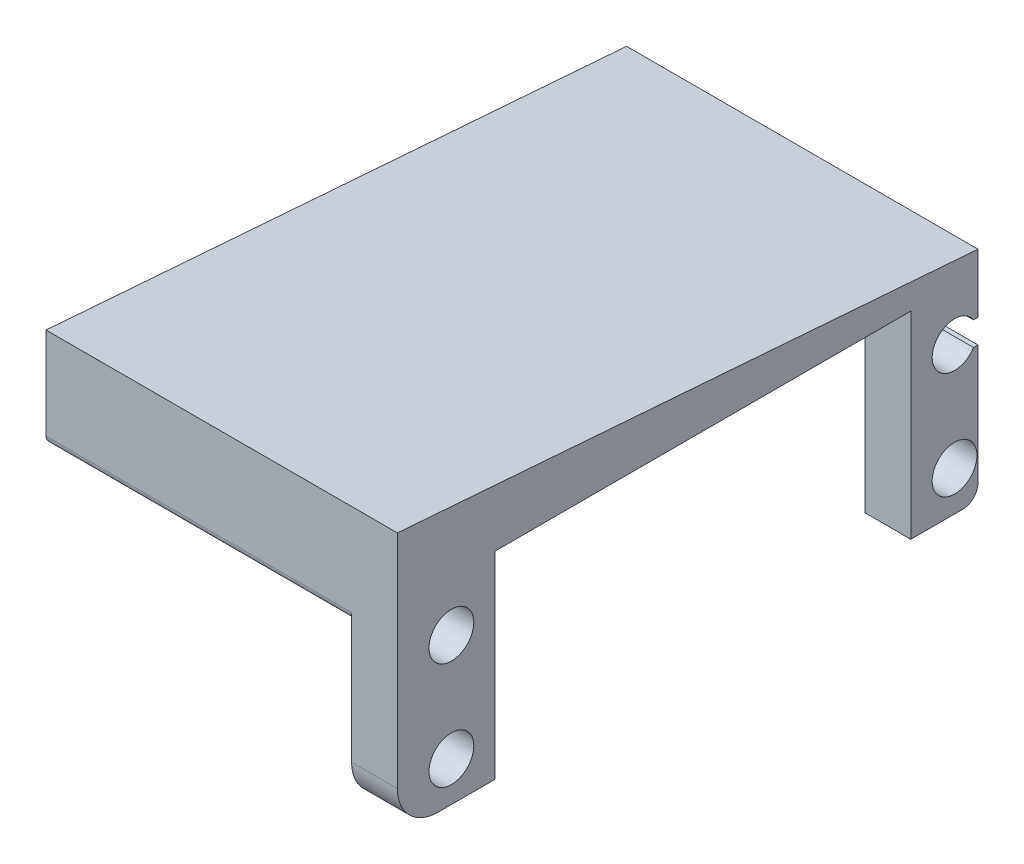
SolidWorks part; units mm, degrees
note: The reader was unsure of these and kept them because the rebuilt part matched: shared geometry of "Sketch1<3>".
ref_plane "Front Plane" through (0, 0, 0) normal (0, 0, 1) x (1, 0, 0)
ref_plane "Top Plane" through (0, 0, 0) normal (0, 1, 0) x (1, 0, 0)
ref_plane "Right Plane" through (0, 0, 0) normal (1, 0, 0) x (0, 0, -1)
sketch "Sketch1" plane through (-110.0403, 0, 0) normal (1, 0, 0) x (0, 0, -1)
  line L0 (162.7914, 64.5774) -> (162.7914, 42.8318)
  line L1 (120.2575, 67.8436) -> (219.7914, 60.2005) construction
  line L2 (166.7914, 38.8318) -> (172.3914, 38.8318)
  line L3 (172.3914, 38.8318) -> (172.3914, 58.2318)
  line L4 (172.3914, 58.2318) -> (213.1914, 58.2318)
  line L5 (213.1914, 58.2318) -> (213.1914, 38.8318)
  line L6 (213.1914, 38.8318) -> (218.2914, 38.8318)
  line L7 (219.7914, 23.5318) -> (219.7914, 57.2005) construction
  line L8 (219.7914, 40.3318) -> (219.7914, 60.2005)
  line L9 (219.7914, 60.2005) -> (162.7914, 64.5774)
  line L10 (172.7914, 47.9818) -> (212.7914, 47.9818) construction
  line L11 (172.7914, 57.2318) -> (172.7914, 38.7318) construction
  line L12 (192.7914, 47.9818) -> (192.7914, 38.2318) construction
  line L13 (173.2914, 38.2318) -> (203.0414, 38.2318) construction
  line L14 (212.7914, 38.7318) -> (212.7914, 47.9818) construction
  line L15 (212.7914, 38.8318) -> (218.7914, 38.8318) construction
  line L16 (203.0414, 57.7318) -> (173.2914, 57.7318) construction
  line L17 (165.7914, 52.0568) -> (165.7914, 48.7318) construction
  line L18 (172.3914, 57.4318) -> (165.4914, 57.4318)
  line L19 (165.4914, 57.4318) -> (165.4914, 54.8075)
  line L20 (165.4914, 54.8075) -> (162.7914, 54.8075)
  line L21 (213.1914, 57.4318) -> (219.7914, 57.4318)
  line L22 (218.7914, 57.1318) -> (212.7914, 57.1318) construction
  line L23 (165.7914, 56.1318) -> (165.7914, 54.4068) construction
  line L24 (158.5875, 49.8075) -> (163.5166, 49.8075) construction
  circle A0 centre (217.4914, 53.2318) radius 2.2
  circle A1 centre (217.4914, 42.7318) radius 2.2
  arc A2 (219.3514, 43.9068) -> (219.3514, 41.5568) centre (217.4914, 42.7318) ccw construction
  arc A3 (219.3514, 54.4068) -> (219.3514, 52.0568) centre (217.4914, 53.2318) ccw construction
  circle A4 centre (168.0914, 53.2318) radius 2.2
  arc A5 (166.2315, 52.0568) -> (166.2315, 54.4068) centre (168.0914, 53.2318) ccw construction
  circle A6 centre (168.0914, 42.7318) radius 2.2
  arc A7 (166.2315, 41.5568) -> (166.2315, 43.9068) centre (168.0914, 42.7318) ccw construction
  arc A8 (218.2914, 38.8318) -> (219.7914, 40.3318) centre (218.2914, 40.3318) ccw
  arc A9 (162.7914, 42.8318) -> (166.7914, 38.8318) centre (166.7914, 42.8318) ccw
  circle A10 centre (163.5414, 55.5575) radius 0.75
  point P52 (219.7914, 38.8318)
  dimension "D4" = 1.5
  dimension "D5" = 4
  dimension "D9" = 1.5
  dimension "D1" = 0.4
  dimension "D2" = 0.5
  dimension "D3" = 3
  dimension "D6" = 0.3
  dimension "D7" = 0.3
  dimension "D8" = 5
extrude "Boss-Extrude1" add sketch "Sketch1" along normal blind 4.5
extrude "Boss-Extrude2" add sketch "Sketch1<3>" against normal blind 30 contours A10 L20 L19 L18 L3 L4 L5 L21 L8 L9 L0 | A10
sketch "Sketch1<3>" plane through (-110.0403, 0, 0) normal (1, 0, 0) x (0, 0, -1) same geometry as "Sketch1"
